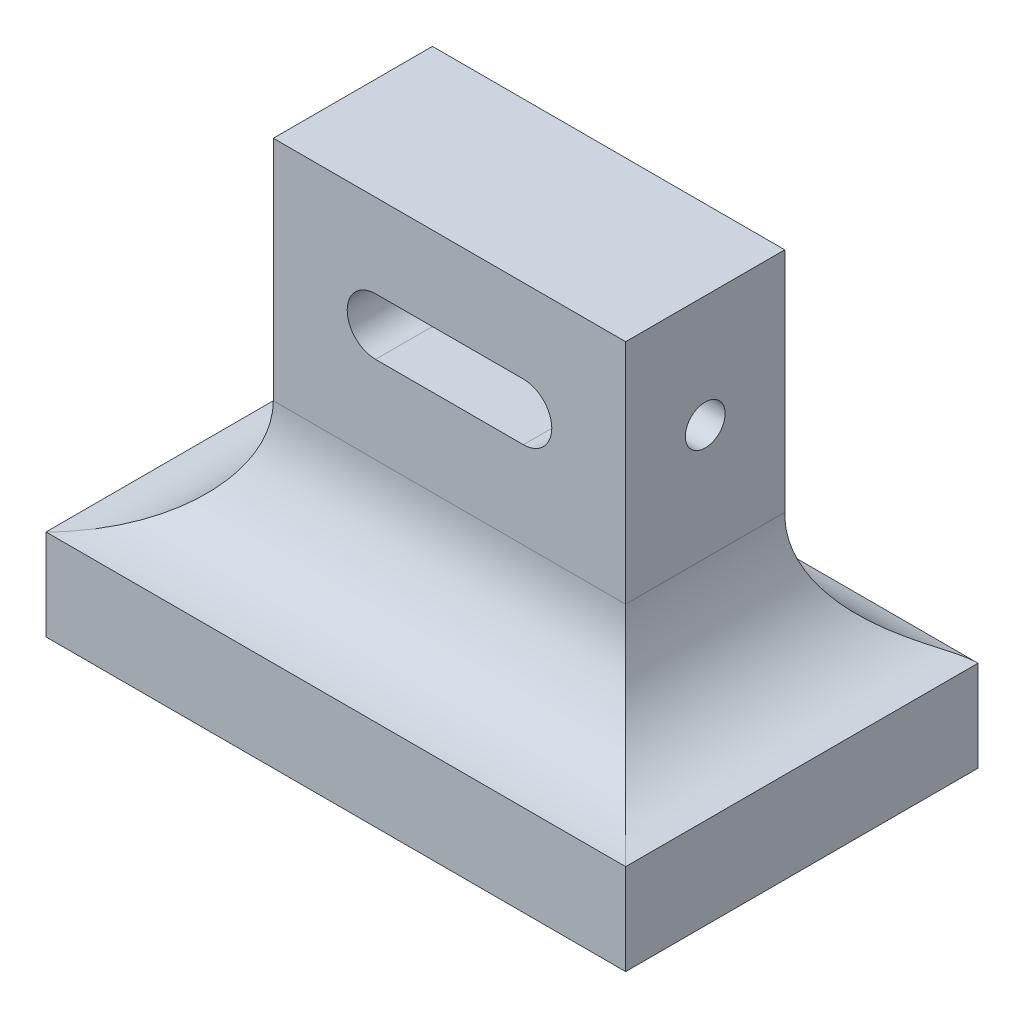
SolidWorks part; units mm, degrees
ref_plane "Front Plane" through (0, 0, 0) normal (0, 0, 1) x (1, 0, 0)
ref_plane "Top Plane" through (0, 0, 0) normal (0, 1, 0) x (1, 0, 0)
ref_plane "Right Plane" through (0, 0, 0) normal (1, 0, 0) x (0, 0, -1)
sketch "Sketch1" plane through (0, 0, 0) normal (0, 1, 0) x (1, 0, 0)
  line L1 (0, 0) -> (51, 0)
  line L2 (0, 0) -> (0, 31)
  line L3 (0, 31) -> (51, 31)
  line L4 (51, 0) -> (51, 31)
  dimension "D1" = 51
  dimension "D2" = 31
extrude "Boss-Extrude1" add sketch "Sketch1" along normal blind 8
ref_plane "Plane1" through (0, 0, -15.5) normal (0, 0, 1) x (1, 0, 0)
sketch "Sketch5" plane through (0, 8, 0) normal (0, 1, 0) x (1, 0, 0)
  line L0 (51, 31) -> (0, 31) construction
  line L1 (41, 24) -> (10, 24)
  line L2 (41, 24) -> (41, 10)
  line L3 (41, 10) -> (10, 10)
  line L4 (10, 24) -> (10, 10)
  line L5 (25.5, 24) -> (25.5, 10) construction
  line L6 (25.5, 31) -> (25.5, 0) construction
  line L7 (0, 0) -> (51, 0) construction
  dimension "D1" = 7
  dimension "D2" = 31
  dimension "D3" = 14
extrude "Boss-Extrude3" add sketch "Sketch5" along normal blind 30 contours L1 L4 L3 L2
sketch "Sketch6" plane through (0, 0, -24) normal (0, 0, -1) x (-1, 0, 0)
  line L0 (-41, 28.15) -> (-10, 28.15) construction
  line L1 (-41, 38) -> (-41, 8) construction
  line L2 (-10, 38) -> (-10, 8) construction
  line L3 (-41, 8) -> (-10, 8) construction
  line L4 (-32, 30.65) -> (-19, 30.65)
  line L5 (-25.5, 38) -> (-25.5, 8) construction
  line L6 (-41, 38) -> (-10, 38) construction
  line L7 (-32, 25.65) -> (-19, 25.65)
  arc A0 (-32, 25.65) -> (-32, 30.65) centre (-32, 28.15) cw
  arc A1 (-19, 25.65) -> (-19, 30.65) centre (-19, 28.15) ccw
  point P14 (-25.5, 30.65)
  dimension "D2" = 2.5
  dimension "D3" = 2.5
  dimension "D5" = 13
  dimension "D1" = 20.15
  dimension "D4" = 2.5
extrude "Cut-Extrude3" cut sketch "Sketch6" against normal through all
fillet "Fillet1" radius 10 4 edges at (25.5, 8, -24) (10, 8, -17) (41, 8, -17) (25.5, 8, -10)
sketch "Sketch8" plane through (41, 0, 0) normal (1, 0, 0) x (0, 0, -1)
  line L0 (10, 25.65) -> (24, 25.65) construction
  line L1 (10, 38) -> (10, 18) construction
  line L2 (24, 38) -> (24, 18) construction
  line L3 (24, 30.65) -> (10, 30.65) construction
  line L4 (17, 30.65) -> (17, 25.65) construction
  circle A0 centre (17, 28.15) radius 1.75
  point P16 (17, 28.15)
  dimension "D1" = 3.5
extrude "3.5mm screw hole for tensioning" cut sketch "Sketch8" against normal through all
